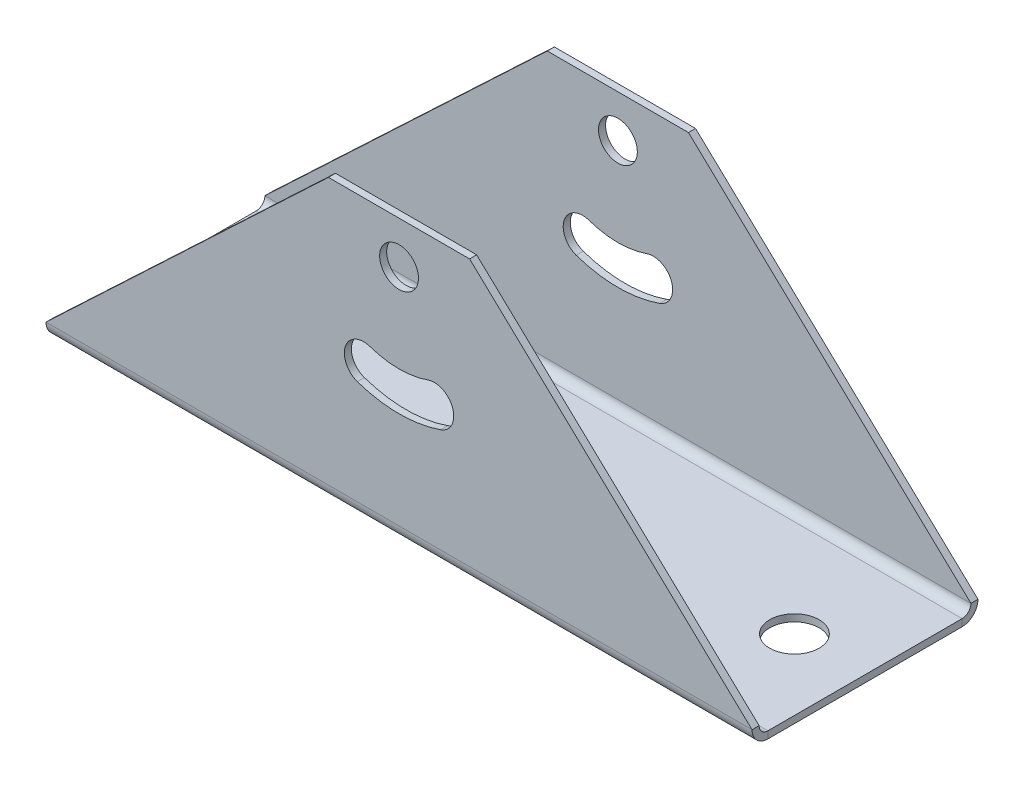
SolidWorks part; units mm, degrees
note: The reader was unsure of these and kept them because the rebuilt part matched: flange length of "Edge-Flange2".
material "AISI 304"
ref_plane "Front Plane" through (0, 0, 0) normal (0, 0, 1) x (1, 0, 0)
ref_plane "Top Plane" through (0, 0, 0) normal (0, 1, 0) x (1, 0, 0)
ref_plane "Right Plane" through (0, 0, 0) normal (1, 0, 0) x (0, 0, -1)
sketch "Sketch9" plane through (0, 0, 0) normal (0, 1, 0) x (1, 0, 0)
  line L1 (-100, -32) -> (100, -32)
  line L2 (-100, -32) -> (-100, 32)
  line L3 (-100, 32) -> (100, 32)
  line L4 (100, -32) -> (100, 32)
  line L5 (-100, -32) -> (100, 32) construction
  line L6 (-100, 32) -> (100, -32) construction
  point P0 (0, 0)
  dimension "D1" = 200
  dimension "D2" = 64
base flange "Base-Flange2" sketch "Sketch9" thickness 2 reverse thickness direction no parameters "D1"=2.5
edge flange "Edge-Flange2" sketch "Sketch18" flange profiles "Sketch18", "Sketch19" flange angle 90 flange length 80 flange position material inside bend radius 2.5 thickness 2 relief obround parameters "D6"=10, "D8"=1
sketch "Sketch18" plane through (0, 0, 32) normal (0, 0, -1) x (-1, 0, 0)
  line L2 (-100, 0) -> (-100, 78)
  line L3 (-100, 78) -> (100, 78)
  line L4 (100, 78) -> (100, 0)
  line L5 (100, 0) -> (-100, 0) construction
  line L6 (100, 0) -> (-100, 0)
sketch "Sketch19" plane through (0, 0, -32) normal (0, 0, 1) x (1, 0, 0)
  line L2 (-100, 0) -> (-100, 78)
  line L3 (-100, 78) -> (100, 78)
  line L4 (100, 78) -> (100, 0)
  line L5 (100, 0) -> (-100, 0) construction
  line L6 (100, 0) -> (-100, 0)
bend "EdgeBend2" bend radius 2.5 bend angle 90 parameters "D5"=1
bend "EdgeBend3" bend radius 2.5 bend angle 90 parameters "D5"=2
sketch "Sketch20" plane through (0, 0, 32) normal (0, 0, 1) x (1, 0, 0)
  line L0 (-100, 2.5) -> (-20, 78)
  line L1 (-100, 78) -> (100, 78) construction
  line L2 (-20, 78) -> (-100, 78)
  line L3 (-100, 78) -> (-100, 2.5)
  line L4 (-100, 2.5) -> (-100, -2) construction
  dimension "D1" = 80
extrude "Cut-Extrude1" cut sketch "Sketch20" against normal through all normal cut yes
mirror "Mirror1" about plane through (0, 0, 0) normal (1, 0, 0) of "Cut-Extrude1"
sketch "Sketch21" plane through (0, 0, 32) normal (0, 0, 1) x (1, 0, 0)
  line L0 (-20, 78) -> (20, 78) construction
  circle A0 centre (0, 66) radius 5.5
  dimension "D1" = 11
  dimension "D2" = 12
extrude "Cut-Extrude2" cut sketch "Sketch21" against normal through all normal cut yes
sketch "Sketch22" plane through (0, 0, 32) normal (0, 0, 1) x (1, 0, 0)
  arc A0 (10, 37.1859) -> (-10, 37.1859) centre (0, 66) cw construction
  arc A1 (-11.8033, 31.99) -> (11.8033, 31.99) centre (0, 66) ccw
  arc A2 (-8.1967, 42.3819) -> (8.1967, 42.3819) centre (0, 66) ccw
  arc A3 (-8.1967, 42.3819) -> (-11.8033, 31.99) centre (-10, 37.1859) ccw
  arc A4 (11.8033, 31.99) -> (8.1967, 42.3819) centre (10, 37.1859) ccw
  circle A5 centre (0, 66) radius 5.5 construction
  point P3 (0, 35.5)
  dimension "D4" = 25
  dimension "D1" = 20
  dimension "D2" = 30.5
extrude "Cut-Extrude3" cut sketch "Sketch22" against normal through all normal cut yes
sketch "Sketch23" plane through (0, 0, 0) normal (0, 1, 0) x (1, 0, 0)
  line L1 (100, -27.5) -> (100, 27.5) construction
  circle A0 centre (-80, 0) radius 7
  circle A1 centre (80, 0) radius 7
  dimension "D1" = 14
  dimension "D3" = 20
  dimension "D2" = 160
extrude "Cut-Extrude4" cut sketch "Sketch23" against normal blind 10 normal cut yes
sketch "Bend-Lines3" [suppressed] plane through (0, 0, 0) normal (0, 1, 0) x (1, 0, 0)
sketch "Bounding-Box3" [suppressed] plane through (0, 0, 0) normal (0, 1, 0) x (1, 0, 0)
sheet metal parameters "Sheet-Metal3" thickness 2 parameters "D1"=2.5
flat pattern "Flat-Pattern3" [suppressed]
sketch "Bend-Lines4" plane through (0, 0, 0) normal (0, 1, 0) x (1, 0, 0)
sketch3d "Bounding-Box4" [suppressed]
  line L0 (-80, 20, 0) -> (80, 20, 0) construction
  line L1 (-80, -20, 0) -> (80, -20, 0) construction
  line L2 (-80, 20, 0) -> (-80, -20, 0) construction
  line L3 (80, 20, 0) -> (80, -20, 0) construction
sheet metal parameters "Sheet-Metal4" thickness 2 parameters "D1"=2.5
flat pattern "Flat-Pattern3"
sketch "Bend-Lines4" plane through (0, 0, 0) normal (0, 1, 0) x (1, 0, 0)
  line L0 (80, 18.0918) -> (-80, 18.0918) construction
  line L1 (-80, -18.0918) -> (80, -18.0918) construction
  line L2 (80, 18.0918) -> (-80, 18.0918) construction
  line L3 (-80, -18.0918) -> (80, -18.0918) construction
sketch3d "Bounding-Box4" [suppressed]
  line L0 (-80, -96.1836, 0) -> (-80, 96.1836, 0) construction
  line L1 (80, -96.1836, 0) -> (80, 96.1836, 0) construction
  line L2 (-80, -96.1836, 0) -> (80, -96.1836, 0) construction
  line L3 (-80, 96.1836, 0) -> (80, 96.1836, 0) construction
bend of the flat pattern "Flatten-<EdgeBend2>1"
bend of the flat pattern "Flatten-<EdgeBend3>1"
sheet metal parameters "Sheet-Metal5" thickness 2 parameters "D1"=2.5
flat pattern "Flat-Pattern3"
sketch "Bend-Lines4" plane through (0, 0, 0) normal (0, 1, 0) x (1, 0, 0)
  line L0 (80, 18.0918) -> (-77.3594, 18.0918) construction
  line L1 (-77.3594, -18.0918) -> (80, -18.0918) construction
  line L2 (80, 18.0918) -> (-77.3594, 18.0918) construction
  line L3 (-77.3594, -18.0918) -> (80, -18.0918) construction
sketch3d "Bounding-Box4" [suppressed]
  line L0 (-78.375, -96.1836, 0) -> (-78.375, 96.1836, 0) construction
  line L1 (80, -96.1836, 0) -> (80, 96.1836, 0) construction
  line L2 (-78.375, -96.1836, 0) -> (80, -96.1836, 0) construction
  line L3 (-78.375, 96.1836, 0) -> (80, 96.1836, 0) construction
bend of the flat pattern "Flatten-<EdgeBend2>1"
bend of the flat pattern "Flatten-<EdgeBend3>1"
sheet metal parameters "Sheet-Metal6" thickness 2 parameters "D1"=2.5
flat pattern "Flat-Pattern3"
sketch "Bend-Lines4" plane through (0, 0, 0) normal (0, 1, 0) x (1, 0, 0)
  line L0 (77.3594, 18.0918) -> (-77.3594, 18.0918) construction
  line L1 (-77.3594, -18.0918) -> (77.3594, -18.0918) construction
  line L2 (77.3594, 18.0918) -> (-77.3594, 18.0918) construction
  line L3 (-77.3594, -18.0918) -> (77.3594, -18.0918) construction
sketch3d "Bounding-Box4" [suppressed]
  line L0 (-109.1468, -19.6894, 0) -> (-3.0706, 110.866, 0) construction
  line L1 (3.0706, -110.866, 0) -> (109.1468, 19.6894, 0) construction
  line L2 (-109.1468, -19.6894, 0) -> (3.0706, -110.866, 0) construction
  line L3 (-3.0706, 110.866, 0) -> (109.1468, 19.6894, 0) construction
bend of the flat pattern "Flatten-<EdgeBend2>1"
bend of the flat pattern "Flatten-<EdgeBend3>1"
sheet metal parameters "Sheet-Metal7" thickness 2 parameters "D1"=2.5
flat pattern "Flat-Pattern3"
sketch "Bend-Lines4" plane through (0, 0, 0) normal (0, 1, 0) x (1, 0, 0)
  line L0 (77.3594, 18.0918) -> (-77.3594, 18.0918) construction
  line L1 (-77.3594, -18.0918) -> (77.3594, -18.0918) construction
  line L2 (77.3594, 18.0918) -> (-77.3594, 18.0918) construction
  line L3 (-77.3594, -18.0918) -> (77.3594, -18.0918) construction
sketch3d "Bounding-Box4" [suppressed]
  line L0 (-109.1468, -19.6894, 0) -> (-3.0706, 110.866, 0) construction
  line L1 (3.0706, -110.866, 0) -> (109.1468, 19.6894, 0) construction
  line L2 (-109.1468, -19.6894, 0) -> (3.0706, -110.866, 0) construction
  line L3 (-3.0706, 110.866, 0) -> (109.1468, 19.6894, 0) construction
bend of the flat pattern "Flatten-<EdgeBend2>1"
bend of the flat pattern "Flatten-<EdgeBend3>1"
sheet metal parameters "Sheet-Metal8" thickness 2 parameters "D1"=2.5
flat pattern "Flat-Pattern3"
sketch "Bend-Lines4" plane through (0, 0, 0) normal (0, 1, 0) x (1, 0, 0)
  line L0 (100, 30.0918) -> (-100, 30.0918) construction
  line L1 (-100, -30.0918) -> (100, -30.0918) construction
  line L2 (100, 30.0918) -> (-100, 30.0918) construction
  line L3 (-100, -30.0918) -> (100, -30.0918) construction
sketch3d "Bounding-Box4" [suppressed]
  line L0 (-141.9819, -16.08, 0) -> (-5.2023, 142.7948, 0) construction
  line L1 (5.2023, -142.7948, 0) -> (141.9819, 16.08, 0) construction
  line L2 (-141.9819, -16.08, 0) -> (5.2023, -142.7948, 0) construction
  line L3 (-5.2023, 142.7948, 0) -> (141.9819, 16.08, 0) construction
bend of the flat pattern "Flatten-<EdgeBend2>1"
bend of the flat pattern "Flatten-<EdgeBend3>1"
sheet metal parameters "Sheet-Metal9" thickness 2 parameters "D1"=2.5
flat pattern "Flat-Pattern3"
sketch "Bend-Lines4" plane through (0, 0, 0) normal (0, 1, 0) x (1, 0, 0)
  line L0 (100, 30.0918) -> (-100, 30.0918) construction
  line L1 (-100, -30.0918) -> (100, -30.0918) construction
  line L2 (100, 30.0918) -> (-100, 30.0918) construction
  line L3 (-100, -30.0918) -> (100, -30.0918) construction
sketch3d "Bounding-Box4" [suppressed]
  line L0 (132.6289, 1.8901, 0) -> (-5.7829, 132.5163, 0) construction
  line L1 (5.7829, -132.5163, 0) -> (-132.6289, -1.8901, 0) construction
  line L2 (132.6289, 1.8901, 0) -> (5.7829, -132.5163, 0) construction
  line L3 (-5.7829, 132.5163, 0) -> (-132.6289, -1.8901, 0) construction
bend of the flat pattern "Flatten-<EdgeBend2>1"
bend of the flat pattern "Flatten-<EdgeBend3>1"
